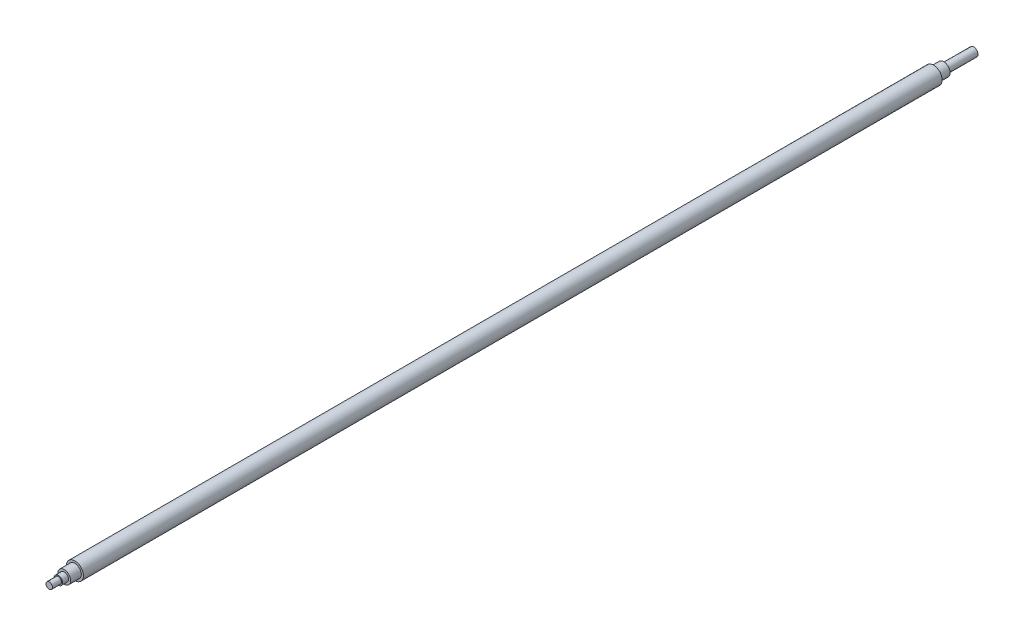
SolidWorks part; units mm, degrees
ref_plane "Piano frontale" through (0, 0, 0) normal (0, 0, 1) x (1, 0, 0)
ref_plane "Piano superiore" through (0, 0, 0) normal (0, 1, 0) x (1, 0, 0)
ref_plane "Piano destro" through (0, 0, 0) normal (1, 0, 0) x (0, 0, -1)
sketch "Schizzo2" plane through (0, 0, 0) normal (1, 0, 0) x (0, 0, -1)
  line L0 (0, 0) -> (0, 3)
  line L1 (0, 3) -> (8.5, 3)
  line L2 (8.5, 3) -> (8.5, 4)
  line L3 (8.5, 4) -> (14, 4)
  line L4 (14, 4) -> (14, 6)
  line L5 (14, 6) -> (24, 6)
  line L6 (24, 6) -> (24, 8)
  line L7 (24, 8) -> (826, 8)
  line L8 (826, 8) -> (826, 6)
  line L9 (826, 6) -> (835.5, 6)
  line L10 (835.5, 6) -> (835.5, 4)
  line L11 (863.5, 0) -> (0, 0)
  line L14 (863.5, 0) -> (863.5, 4)
  line L15 (0, 0) -> (351.0218, 0) construction
  line L18 (835.5, 4) -> (863.5, 4)
  point P33 (0, 0)
  dimension "D2" = 6
  dimension "D3" = 8
  dimension "D4" = 12
  dimension "D5" = 16
  dimension "D6" = 12
  dimension "D7" = 8
  dimension "D8" = 8.5
  dimension "D9" = 5.5
  dimension "D10" = 10
  dimension "D11" = 802
  dimension "D12" = 9.5
  dimension "D13" = 28
  dimension "D14" = 863.5
revolve "Rivoluzione2" add sketch "Schizzo2" angle 360 about L15
